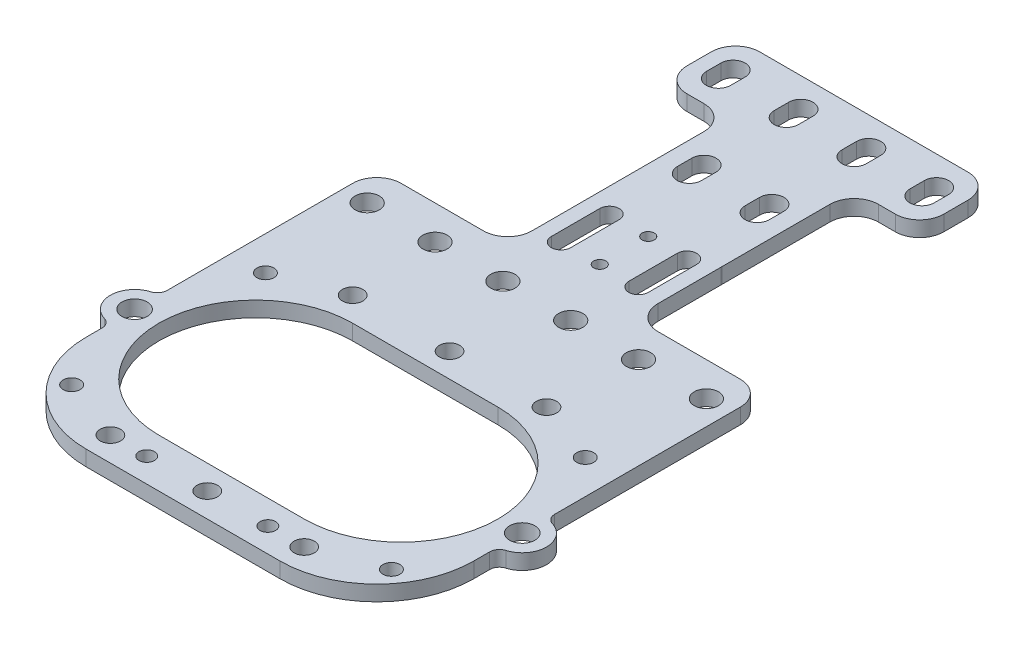
SolidWorks part; units mm, degrees
ref_plane "Front Plane" through (0, 0, 0) normal (0, 0, 1) x (1, 0, 0)
ref_plane "Top Plane" through (0, 0, 0) normal (0, 1, 0) x (1, 0, 0)
ref_plane "Right Plane" through (0, 0, 0) normal (1, 0, 0) x (0, 0, -1)
ref_plane "Plane1" through (0, 32.675, 0) normal (0, 1, 0) x (1, 0, 0)
sketch "Sketch11" plane through (0, 32.675, 0) normal (0, 1, 0) x (1, 0, 0)
  line L0 (222.001, 57.5) -> (222.001, 22)
  line L1 (217.001, 17) -> (200.001, 17)
  line L2 (195.001, 12) -> (195.001, -26.2918)
  line L3 (195.001, -39.7082) -> (195.001, -43)
  line L4 (215.001, -63) -> (255.001, -63)
  line L5 (275.001, -43) -> (275.001, -39.7082)
  line L6 (275.001, -26.2918) -> (275.001, 12)
  line L7 (270.001, 17) -> (253.001, 17)
  line L8 (248.001, 22) -> (248.001, 57.5)
  line L9 (253.001, 62.5) -> (256.501, 62.5)
  line L10 (261.501, 67.5) -> (261.501, 72.5)
  line L11 (256.501, 77.5) -> (213.501, 77.5)
  line L12 (208.501, 72.5) -> (208.501, 67.5)
  line L13 (213.501, 62.5) -> (217.001, 62.5)
  arc A0 (222.001, 22) -> (217.001, 17) centre (217.001, 22) cw
  arc A1 (200.001, 17) -> (195.001, 12) centre (200.001, 12) ccw
  arc A2 (195.001, -26.2918) -> (193.5724, -28.2084) centre (193.001, -26.2918) cw
  arc A3 (193.5724, -28.2084) -> (193.5724, -37.7916) centre (195.001, -33) ccw
  arc A4 (193.5724, -37.7916) -> (195.001, -39.7082) centre (193.001, -39.7082) cw
  arc A5 (195.001, -43) -> (215.001, -63) centre (215.001, -43) ccw
  arc A6 (255.001, -63) -> (275.001, -43) centre (255.001, -43) ccw
  arc A7 (275.001, -39.7082) -> (276.4296, -37.7916) centre (277.001, -39.7082) cw
  arc A8 (276.4296, -37.7916) -> (276.4296, -28.2084) centre (275.001, -33) ccw
  arc A9 (276.4296, -28.2084) -> (275.001, -26.2918) centre (277.001, -26.2918) cw
  arc A10 (275.001, 12) -> (270.001, 17) centre (270.001, 12) ccw
  arc A11 (253.001, 17) -> (248.001, 22) centre (253.001, 22) cw
  arc A12 (248.001, 57.5) -> (253.001, 62.5) centre (253.001, 57.5) cw
  arc A13 (256.501, 62.5) -> (261.501, 67.5) centre (256.501, 67.5) ccw
  arc A14 (261.501, 72.5) -> (256.501, 77.5) centre (256.501, 72.5) ccw
  arc A15 (213.501, 77.5) -> (208.501, 72.5) centre (213.501, 72.5) ccw
  arc A16 (208.501, 67.5) -> (213.501, 62.5) centre (213.501, 67.5) ccw
  arc A17 (217.001, 62.5) -> (222.001, 57.5) centre (217.001, 57.5) cw
base flange "Base-Flange1" sketch "Sketch11" thickness 3.175 reverse thickness direction yes parameters "D1"=0
sketch "Sketch16" plane through (0, 29.5, 0) normal (0, -1, 0) x (1, 0, 0)
  line L0 (222.001, -35) -> (222.001, -35.2301)
  line L1 (222.001, -35.2301) -> (222.0063, -35.2301)
  arc A0 (222.0063, -35.2301) -> (222.001, -35) centre (227.001, -35) cw
extrude "Cut-Extrude1" cut sketch "Sketch16" against normal blind 3.175
sketch "Sketch17" plane through (0, 29.5, 0) normal (0, -1, 0) x (1, 0, 0)
  line L0 (248.001, -35.2301) -> (248.001, -35)
  line L1 (247.9957, -35.2301) -> (248.001, -35.2301)
  arc A0 (248.001, -35) -> (247.9957, -35.2301) centre (243.001, -35) cw
extrude "Cut-Extrude2" cut sketch "Sketch17" against normal blind 3.175
sketch "Sketch18" plane through (0, 32.675, 0) normal (0, 1, 0) x (-1, 0, 0)
  line L0 (-250.001, 13) -> (-220.001, 13)
  line L1 (-220.001, 53) -> (-250.001, 53)
  arc A0 (-220.001, 13) -> (-220.001, 53) centre (-220.001, 33) ccw
  arc A1 (-250.001, 53) -> (-250.001, 13) centre (-250.001, 33) ccw
extrude "Cut-Extrude3" cut sketch "Sketch18" against normal through all
sketch "Sketch19" plane through (0, 32.675, 0) normal (0, 1, 0) x (-1, 0, 0)
  line L0 (-225.001, -33) -> (-225.001, -23)
  line L1 (-229.001, -23) -> (-229.001, -33)
  arc A0 (-225.001, -23) -> (-229.001, -23) centre (-227.001, -23) ccw
  arc A1 (-229.001, -33) -> (-225.001, -33) centre (-227.001, -33) ccw
extrude "Cut-Extrude4" cut sketch "Sketch19" against normal through all
sketch "Sketch20" plane through (0, 32.675, 0) normal (0, 1, 0) x (-1, 0, 0)
  line L0 (-241.001, -33) -> (-241.001, -23)
  line L1 (-245.001, -23) -> (-245.001, -33)
  arc A0 (-241.001, -23) -> (-245.001, -23) centre (-243.001, -23) ccw
  arc A1 (-245.001, -33) -> (-241.001, -33) centre (-243.001, -33) ccw
extrude "Cut-Extrude5" cut sketch "Sketch20" against normal through all
sketch "Sketch21" plane through (0, 32.675, 0) normal (0, 1, 0) x (-1, 0, 0)
  line L0 (-225.501, -51.5) -> (-225.501, -48.5)
  line L1 (-230.501, -48.5) -> (-230.501, -51.5)
  arc A0 (-225.501, -48.5) -> (-230.501, -48.5) centre (-228.001, -48.5) ccw
  arc A1 (-230.501, -51.5) -> (-225.501, -51.5) centre (-228.001, -51.5) ccw
extrude "Cut-Extrude6" cut sketch "Sketch21" against normal through all
sketch "Sketch22" plane through (0, 32.675, 0) normal (0, 1, 0) x (-1, 0, 0)
  line L0 (-239.501, -51.5) -> (-239.501, -48.5)
  line L1 (-244.501, -48.5) -> (-244.501, -51.5)
  arc A0 (-239.501, -48.5) -> (-244.501, -48.5) centre (-242.001, -48.5) ccw
  arc A1 (-244.501, -51.5) -> (-239.501, -51.5) centre (-242.001, -51.5) ccw
extrude "Cut-Extrude7" cut sketch "Sketch22" against normal through all
sketch "Sketch23" plane through (0, 32.675, 0) normal (0, 1, 0) x (-1, 0, 0)
  line L0 (-211.501, -71.5) -> (-211.501, -68.5)
  line L1 (-216.501, -68.5) -> (-216.501, -71.5)
  arc A0 (-211.501, -68.5) -> (-216.501, -68.5) centre (-214.001, -68.5) ccw
  arc A1 (-216.501, -71.5) -> (-211.501, -71.5) centre (-214.001, -71.5) ccw
extrude "Cut-Extrude8" cut sketch "Sketch23" against normal through all
sketch "Sketch24" plane through (0, 32.675, 0) normal (0, 1, 0) x (-1, 0, 0)
  line L0 (-225.501, -71.5) -> (-225.501, -68.5)
  line L1 (-230.501, -68.5) -> (-230.501, -71.5)
  arc A0 (-225.501, -68.5) -> (-230.501, -68.5) centre (-228.001, -68.5) ccw
  arc A1 (-230.501, -71.5) -> (-225.501, -71.5) centre (-228.001, -71.5) ccw
extrude "Cut-Extrude9" cut sketch "Sketch24" against normal through all
sketch "Sketch25" plane through (0, 32.675, 0) normal (0, 1, 0) x (-1, 0, 0)
  line L0 (-239.501, -71.5) -> (-239.501, -68.5)
  line L1 (-244.501, -68.5) -> (-244.501, -71.5)
  arc A0 (-239.501, -68.5) -> (-244.501, -68.5) centre (-242.001, -68.5) ccw
  arc A1 (-244.501, -71.5) -> (-239.501, -71.5) centre (-242.001, -71.5) ccw
extrude "Cut-Extrude10" cut sketch "Sketch25" against normal through all
sketch "Sketch26" plane through (0, 29.5, 0) normal (0, -1, 0) x (1, 0, 0)
  line L0 (253.501, -68.5) -> (253.501, -71.5)
  line L1 (258.501, -71.5) -> (258.501, -68.5)
  arc A0 (253.501, -71.5) -> (258.501, -71.5) centre (256.001, -71.5) ccw
  arc A1 (258.501, -68.5) -> (253.501, -68.5) centre (256.001, -68.5) ccw
extrude "Cut-Extrude11" cut sketch "Sketch26" against normal through all
hole_wizard "Ø4.2 (4.2) Diameter Hole1" positions "Sketch28" profile "Sketch27" hole size "Ø4.2" standard "ANSI Metric"
sketch "Sketch28" plane through (0, 32.675, 0) normal (0, 1, 0) x (1, 0, 0)
  point P0 (215.001, -8)
  point P1 (215.001, -58)
  point P2 (255.001, -8)
  point P3 (235.001, -58)
  point P4 (255.001, -58)
  point P5 (235.001, -8)
sketch "Sketch27" plane through (215.001, 32.675, 8) normal (1, 0, 0) x (0, 0, 1)
  line L0 (0, 0) -> (0, 3.175)
  line L1 (0, 3.175) -> (2.1, 3.175)
  line L2 (2.1, 3.175) -> (2.1, 0)
  line L5 (2.1, 0) -> (0, 0)
  line L11 (0, -6.35) -> (0, 107.95) construction
  dimension "Thru Hole Dia." = 4.2
  dimension "Thru Hole Depth" = 3.175
hole_wizard "Ø5.2 (5.2) Diameter Hole1" positions "Sketch30" profile "Sketch29" hole size "Ø5.2" standard "ANSI Metric"
sketch "Sketch30" plane through (0, 32.675, 0) normal (0, 1, 0) x (1, 0, 0)
  point P0 (275.001, -33)
  point P1 (195.001, -33)
sketch "Sketch29" plane through (275.001, 32.675, 33) normal (1, 0, 0) x (0, 0, 1)
  line L0 (0, 0) -> (0, 3.175)
  line L1 (0, 3.175) -> (2.6, 3.175)
  line L2 (2.6, 3.175) -> (2.6, 0)
  line L5 (2.6, 0) -> (0, 0)
  line L11 (0, -6.35) -> (0, 107.95) construction
  dimension "Thru Hole Dia." = 5.2
  dimension "Thru Hole Depth" = 3.175
hole_wizard "Ø3.5 (3.5) Diameter Hole1" positions "Sketch32" profile "Sketch31" hole size "Ø3.5" standard "ANSI Metric"
sketch "Sketch32" plane through (0, 32.675, 0) normal (0, 1, 0) x (1, 0, 0)
  point P0 (202.001, -53)
  point P1 (268.001, -13)
  point P2 (202.001, -13)
  point P3 (268.001, -53)
sketch "Sketch31" plane through (202.001, 32.675, 53) normal (1, 0, 0) x (0, 0, 1)
  line L0 (0, 0) -> (0, 3.175)
  line L1 (0, 3.175) -> (1.75, 3.175)
  line L2 (1.75, 3.175) -> (1.75, 0)
  line L5 (1.75, 0) -> (0, 0)
  line L11 (0, -6.35) -> (0, 107.95) construction
  dimension "Thru Hole Dia." = 3.5
  dimension "Thru Hole Depth" = 3.175
hole_wizard "Ø3.2 (3.2) Diameter Hole1" positions "Sketch34" profile "Sketch33" hole size "Ø3.2" standard "ANSI Metric"
sketch "Sketch34" plane through (0, 32.675, 0) normal (0, 1, 0) x (1, 0, 0)
  point P0 (247.501, -58)
  point P1 (222.501, -58)
sketch "Sketch33" plane through (247.501, 32.675, 58) normal (1, 0, 0) x (0, 0, 1)
  line L0 (0, 0) -> (0, 3.175)
  line L1 (0, 3.175) -> (1.6, 3.175)
  line L2 (1.6, 3.175) -> (1.6, 0)
  line L5 (1.6, 0) -> (0, 0)
  line L11 (0, -6.35) -> (0, 107.95) construction
  dimension "Thru Hole Dia." = 3.2
  dimension "Thru Hole Depth" = 3.175
hole_wizard "Ø5.0 (5) Diameter Hole1" positions "Sketch36" profile "Sketch35" hole size "Ø5.0" standard "ANSI Metric"
sketch "Sketch36" plane through (0, 32.675, 0) normal (0, 1, 0) x (1, 0, 0)
  point P0 (242.001, 10)
  point P1 (228.001, 10)
  point P2 (270.001, 10)
  point P3 (256.001, 10)
  point P4 (214.001, 10)
  point P5 (200.001, 10)
sketch "Sketch35" plane through (242.001, 32.675, -10) normal (1, 0, 0) x (0, 0, 1)
  line L0 (0, 0) -> (0, 3.175)
  line L1 (0, 3.175) -> (2.5, 3.175)
  line L2 (2.5, 3.175) -> (2.5, 0)
  line L5 (2.5, 0) -> (0, 0)
  line L11 (0, -6.35) -> (0, 107.95) construction
  dimension "Thru Hole Dia." = 5
  dimension "Thru Hole Depth" = 3.175
hole_wizard "Ø2.5 (2.5) Diameter Hole1" positions "Sketch38" profile "Sketch37" hole size "Ø2.5" standard "ANSI Metric"
sketch "Sketch38" plane through (0, 32.675, 0) normal (0, 1, 0) x (1, 0, 0)
  point P0 (235.001, 23)
  point P1 (235.001, 33)
sketch "Sketch37" plane through (235.001, 32.675, -23) normal (1, 0, 0) x (0, 0, 1)
  line L0 (0, 0) -> (0, 3.175)
  line L1 (0, 3.175) -> (1.25, 3.175)
  line L2 (1.25, 3.175) -> (1.25, 0)
  line L5 (1.25, 0) -> (0, 0)
  line L11 (0, -6.35) -> (0, 107.95) construction
  dimension "Thru Hole Dia." = 2.5
  dimension "Thru Hole Depth" = 3.175
ref_point "Point1"
ref_plane "Plane2" through (0, 0, -70) normal (0, 0, -1) x (-1, 0, 0)
ref_plane "Plane3" through (228.001, 0, 0) normal (-1, 0, 0) x (0, 0, 1)
ref_plane "Plane4" through (242.001, 0, 0) normal (-1, 0, 0) x (0, 0, 1)
sketch "Bend-Lines4" plane through (0, 0, 0) normal (0, 1, 0) x (1, 0, 0)
sketch "Bounding-Box4" plane through (0, 0, 0) normal (0, 1, 0) x (1, 0, 0)
sheet metal parameters "Sheet-Metal(6)" thickness 3.175 parameters "D1"=0
flat pattern "Flat-Pattern(6)" [suppressed]
sketch "Bend-Lines5" plane through (0, 0, 0) normal (0, 1, 0) x (1, 0, 0)
sketch "Bounding-Box5" [suppressed] plane through (0, 0, 0) normal (0, 1, 0) x (1, 0, 0)
sheet metal parameters "Sheet-Metal(7)" thickness 3.175 parameters "D1"=0
flat pattern "Flat-Pattern(6)"
sketch "Bend-Lines5" plane through (0, 0, 0) normal (0, 1, 0) x (1, 0, 0)
sketch "Bounding-Box5" [suppressed] plane through (0, 0, 0) normal (0, 1, 0) x (1, 0, 0)
sheet metal parameters "Sheet-Metal(8)" thickness 3.175 parameters "D1"=0
flat pattern "Flat-Pattern(6)"
sketch "Bend-Lines5" plane through (0, 0, 0) normal (0, 1, 0) x (1, 0, 0)
sketch "Bounding-Box5" [suppressed] plane through (0, 0, 0) normal (0, 1, 0) x (1, 0, 0)
sheet metal parameters "Sheet-Metal(9)" thickness 3.175 parameters "D1"=0
flat pattern "Flat-Pattern(6)"
sketch "Bend-Lines5" plane through (0, 0, 0) normal (0, 1, 0) x (1, 0, 0)
sketch "Bounding-Box5" [suppressed] plane through (0, 0, 0) normal (0, 1, 0) x (1, 0, 0)
sheet metal parameters "Sheet-Metal(10)" thickness 3.175 parameters "D1"=0
flat pattern "Flat-Pattern(6)"
sketch "Bend-Lines5" plane through (0, 0, 0) normal (0, 1, 0) x (1, 0, 0)
sketch "Bounding-Box5" [suppressed] plane through (0, 0, 0) normal (0, 1, 0) x (1, 0, 0)
sheet metal parameters "Sheet-Metal(11)" thickness 3.175 parameters "D1"=0
flat pattern "Flat-Pattern(6)"
sketch "Bend-Lines5" plane through (0, 0, 0) normal (0, 1, 0) x (1, 0, 0)
sketch "Bounding-Box5" [suppressed] plane through (0, 0, 0) normal (0, 1, 0) x (1, 0, 0)
sheet metal parameters "Sheet-Metal(12)" thickness 3.175 parameters "D1"=0
flat pattern "Flat-Pattern(6)"
sketch "Bend-Lines5" plane through (0, 0, 0) normal (0, 1, 0) x (1, 0, 0)
sketch "Bounding-Box5" [suppressed] plane through (0, 0, 0) normal (0, 1, 0) x (1, 0, 0)
sheet metal parameters "Sheet-Metal(13)" thickness 3.175 parameters "D1"=0
flat pattern "Flat-Pattern(6)"
sketch "Bend-Lines5" plane through (0, 0, 0) normal (0, 1, 0) x (1, 0, 0)
sketch "Bounding-Box5" [suppressed] plane through (0, 0, 0) normal (0, 1, 0) x (1, 0, 0)
sheet metal parameters "Sheet-Metal(14)" thickness 3.175 parameters "D1"=0
flat pattern "Flat-Pattern(6)"
sketch "Bend-Lines5" plane through (0, 0, 0) normal (0, 1, 0) x (1, 0, 0)
sketch "Bounding-Box5" [suppressed] plane through (0, 0, 0) normal (0, 1, 0) x (1, 0, 0)
sheet metal parameters "Sheet-Metal(15)" thickness 3.175 parameters "D1"=0
flat pattern "Flat-Pattern(6)"
sketch "Bend-Lines5" plane through (0, 0, 0) normal (0, 1, 0) x (1, 0, 0)
sketch "Bounding-Box5" [suppressed] plane through (0, 0, 0) normal (0, 1, 0) x (1, 0, 0)
sheet metal parameters "Sheet-Metal(16)" thickness 3.175 parameters "D1"=0
flat pattern "Flat-Pattern(6)"
sketch "Bend-Lines5" plane through (0, 0, 0) normal (0, 1, 0) x (1, 0, 0)
sketch "Bounding-Box5" [suppressed] plane through (0, 0, 0) normal (0, 1, 0) x (1, 0, 0)
sheet metal parameters "Sheet-Metal(17)" thickness 3.175 parameters "D1"=0
flat pattern "Flat-Pattern(6)"
sketch "Bend-Lines5" plane through (0, 0, 0) normal (0, 1, 0) x (1, 0, 0)
sketch "Bounding-Box5" [suppressed] plane through (0, 0, 0) normal (0, 1, 0) x (1, 0, 0)
sheet metal parameters "Sheet-Metal(18)" thickness 3.175 parameters "D1"=0
flat pattern "Flat-Pattern(6)"
sketch "Bend-Lines5" plane through (0, 0, 0) normal (0, 1, 0) x (1, 0, 0)
sketch "Bounding-Box5" [suppressed] plane through (0, 0, 0) normal (0, 1, 0) x (1, 0, 0)
sheet metal parameters "Sheet-Metal(19)" thickness 3.175 parameters "D1"=0
flat pattern "Flat-Pattern(6)"
sketch "Bend-Lines5" plane through (0, 0, 0) normal (0, 1, 0) x (1, 0, 0)
sketch "Bounding-Box5" [suppressed] plane through (0, 0, 0) normal (0, 1, 0) x (1, 0, 0)
sheet metal parameters "Sheet-Metal(20)" thickness 3.175 parameters "D1"=0
flat pattern "Flat-Pattern(6)"
sketch "Bend-Lines5" plane through (0, 0, 0) normal (0, 1, 0) x (1, 0, 0)
sketch "Bounding-Box5" [suppressed] plane through (0, 0, 0) normal (0, 1, 0) x (1, 0, 0)
sheet metal parameters "Sheet-Metal(21)" thickness 3.175 parameters "D1"=0
flat pattern "Flat-Pattern(6)"
sketch "Bend-Lines5" plane through (0, 0, 0) normal (0, 1, 0) x (1, 0, 0)
sketch "Bounding-Box5" [suppressed] plane through (0, 0, 0) normal (0, 1, 0) x (1, 0, 0)
sheet metal parameters "Sheet-Metal(22)" thickness 3.175 parameters "D1"=0
flat pattern "Flat-Pattern(6)"
sketch "Bend-Lines5" plane through (0, 0, 0) normal (0, 1, 0) x (1, 0, 0)
sketch "Bounding-Box5" [suppressed] plane through (0, 0, 0) normal (0, 1, 0) x (1, 0, 0)
sheet metal parameters "Sheet-Metal(23)" thickness 3.175 parameters "D1"=0
flat pattern "Flat-Pattern(6)"
sketch "Bend-Lines5" plane through (0, 0, 0) normal (0, 1, 0) x (1, 0, 0)
sketch "Bounding-Box5" [suppressed] plane through (0, 0, 0) normal (0, 1, 0) x (1, 0, 0)
